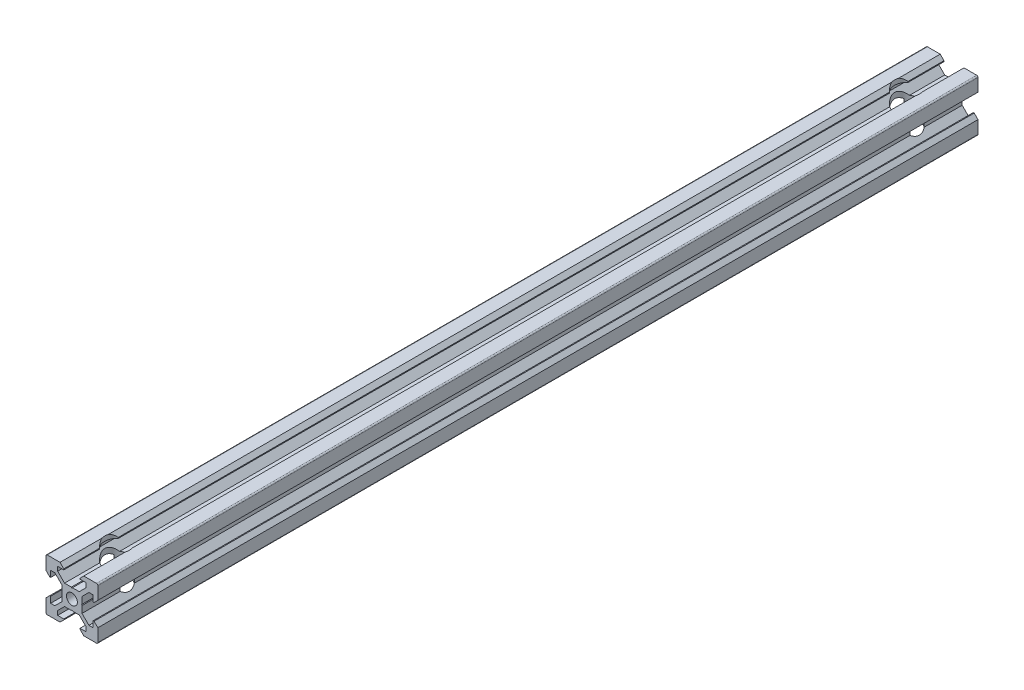
SolidWorks part; units mm, degrees
material "6063-O, Extruded Rod (SS)"
ref_plane "Front Plane" through (0, 0, 0) normal (0, 0, 1) x (1, 0, 0)
ref_plane "Top Plane" through (0, 0, 0) normal (0, 1, 0) x (1, 0, 0)
ref_plane "Right Plane" through (0, 0, 0) normal (1, 0, 0) x (0, 0, -1)
ref_plane "Plane1" through (0, 0, 0) normal (0, 0, -1) x (-1, 0, 0)
sketch "Sketch1" plane through (0, 0, 0) normal (0, 0, -1) x (-1, 0, 0)
  line L0 (-3.9, -0.21) -> (-3.9, -2.8393)
  line L1 (-3.9, -2.8393) -> (-6.5607, -5.5)
  line L2 (-6.5607, -5.5) -> (-8.2, -5.5)
  line L3 (-8.2, -5.5) -> (-8.2, -3.125)
  line L4 (-8.2, -3.125) -> (-8.545, -3.125)
  line L5 (-8.545, -3.125) -> (-10, -4.58)
  line L6 (-10, -4.58) -> (-10, -9.5)
  line L7 (-9.5, -10) -> (-4.58, -10)
  line L8 (-4.58, -10) -> (-3.125, -8.545)
  line L9 (-3.125, -8.545) -> (-3.125, -8.2)
  line L10 (-3.125, -8.2) -> (-5.5, -8.2)
  line L11 (-5.5, -8.2) -> (-5.5, -6.5607)
  line L12 (-5.5, -6.5607) -> (-2.8393, -3.9)
  line L13 (-2.8393, -3.9) -> (-0.21, -3.9)
  line L14 (-0.21, -3.9) -> (0, -3.69)
  line L15 (0, -3.69) -> (0.21, -3.9)
  line L16 (0.21, -3.9) -> (2.8393, -3.9)
  line L17 (2.8393, -3.9) -> (5.5, -6.5607)
  line L18 (5.5, -6.5607) -> (5.5, -8.2)
  line L19 (5.5, -8.2) -> (3.125, -8.2)
  line L20 (3.125, -8.2) -> (3.125, -8.545)
  line L21 (3.125, -8.545) -> (4.58, -10)
  line L22 (4.58, -10) -> (9.5, -10)
  line L23 (10, -9.5) -> (10, -4.58)
  line L24 (10, -4.58) -> (8.545, -3.125)
  line L25 (8.545, -3.125) -> (8.2, -3.125)
  line L26 (8.2, -3.125) -> (8.2, -5.5)
  line L27 (8.2, -5.5) -> (6.5607, -5.5)
  line L28 (6.5607, -5.5) -> (3.9, -2.8393)
  line L29 (3.9, -2.8393) -> (3.9, -0.21)
  line L30 (3.9, -0.21) -> (3.69, 0)
  line L31 (3.69, 0) -> (3.9, 0.21)
  line L32 (3.9, 0.21) -> (3.9, 2.8393)
  line L33 (3.9, 2.8393) -> (6.5607, 5.5)
  line L34 (6.5607, 5.5) -> (8.2, 5.5)
  line L35 (8.2, 5.5) -> (8.2, 3.125)
  line L36 (8.2, 3.125) -> (8.545, 3.125)
  line L37 (8.545, 3.125) -> (10, 4.58)
  line L38 (10, 4.58) -> (10, 9.5)
  line L39 (9.5, 10) -> (4.58, 10)
  line L40 (4.58, 10) -> (3.125, 8.545)
  line L41 (3.125, 8.545) -> (3.125, 8.2)
  line L42 (3.125, 8.2) -> (5.5, 8.2)
  line L43 (5.5, 8.2) -> (5.5, 6.5607)
  line L44 (5.5, 6.5607) -> (2.8393, 3.9)
  line L45 (2.8393, 3.9) -> (0.21, 3.9)
  line L46 (0.21, 3.9) -> (0, 3.69)
  line L47 (0, 3.69) -> (-0.21, 3.9)
  line L48 (-0.21, 3.9) -> (-2.8393, 3.9)
  line L49 (-2.8393, 3.9) -> (-5.5, 6.5607)
  line L50 (-5.5, 6.5607) -> (-5.5, 8.2)
  line L51 (-5.5, 8.2) -> (-3.125, 8.2)
  line L52 (-3.125, 8.2) -> (-3.125, 8.545)
  line L53 (-3.125, 8.545) -> (-4.58, 10)
  line L54 (-4.58, 10) -> (-9.5, 10)
  line L55 (-10, 9.5) -> (-10, 4.58)
  line L56 (-10, 4.58) -> (-8.545, 3.125)
  line L57 (-8.545, 3.125) -> (-8.2, 3.125)
  line L58 (-8.2, 3.125) -> (-8.2, 5.5)
  line L59 (-8.2, 5.5) -> (-6.5607, 5.5)
  line L60 (-6.5607, 5.5) -> (-3.9, 2.8393)
  line L61 (-3.9, 2.8393) -> (-3.9, 0.21)
  line L62 (-3.9, 0.21) -> (-3.69, 0)
  line L63 (-3.69, 0) -> (-3.9, -0.21)
  circle A0 centre (0, 0) radius 2.1
  arc A1 (-10, -9.5) -> (-9.5, -10) centre (-9.5, -9.5) ccw
  arc A2 (9.5, -10) -> (10, -9.5) centre (9.5, -9.5) ccw
  arc A3 (10, 9.5) -> (9.5, 10) centre (9.5, 9.5) ccw
  arc A4 (-9.5, 10) -> (-10, 9.5) centre (-9.5, 9.5) ccw
extrude "Boss-Extrude1" add sketch "Sketch1" against normal blind 500
ref_plane "cut plane" through (0, 0, 160.35) normal (0, 0, 1) x (1, 0, 0)
split "Split1" trim tools "cut plane" bodies to split 103 resulting bodies 105
sketch "Sketch2" plane through (0, 10, 0) normal (0, 1, 0) x (1, 0, 0)
  line L0 (0, -500) -> (0, -160.35) construction
  line L1 (0, -500) -> (0, -160.35) construction
  line L2 (0, -330.175) -> (-38.7772, -330.175) construction
  circle A0 centre (0, -177.775) radius 4.7625
  circle A1 centre (0, -482.575) radius 4.7625
  dimension "D1" = 9.525
  dimension "D2" = 304.8
  dimension "D3" = 152.4
extrude "Cut-Extrude1" cut sketch "Sketch2" against normal up to surface (20 mm away) up to face at (7.04, -10, 330.175)
hole_wizard "M5x0.8 Tapped Hole1" positions "Sketch4" profile "Sketch5" tap size "M5x0.8" standard "ANSI Metric"
sketch "Sketch4" plane through (0, 0, 500) normal (0, 0, 1) x (1, 0, 0)
  point P0 (0, 0)
sketch "Sketch5" plane through (0, 0, 500) normal (1, 0, 0) x (0, -1, 0)
  line L0 (0, 0) -> (0, 15.2318)
  line L1 (0, 15.2318) -> (2.1, 13.97)
  line L2 (2.1, 13.97) -> (2.1, 0)
  line L5 (2.1, 0) -> (0, 0)
  line L10 (0, 15.2318) -> (-2.1, 13.97) construction
  line L11 (0, -6.35) -> (0, 107.95) construction
  dimension "Tap Drill Dia." = 4.2
  dimension "Tap Drill Depth" = 13.97
  dimension "Drill Angle" = 118
hole_wizard "M5x0.8 Tapped Hole2" positions "Sketch7" profile "Sketch6" tap size "M5x0.8" standard "ANSI Metric"
sketch "Sketch7" plane through (0, 0, 160.35) normal (0, 0, -1) x (-1, 0, 0)
  point P0 (0, 0)
sketch "Sketch6" plane through (0, 0, 160.35) normal (1, 0, 0) x (0, 1, 0)
  line L0 (0, 0) -> (0, 15.2318)
  line L1 (0, 15.2318) -> (2.1, 13.97)
  line L2 (2.1, 13.97) -> (2.1, 0)
  line L5 (2.1, 0) -> (0, 0)
  line L10 (0, 15.2318) -> (-2.1, 13.97) construction
  line L11 (0, -6.35) -> (0, 107.95) construction
  dimension "Tap Drill Dia." = 4.2
  dimension "Tap Drill Depth" = 13.97
  dimension "Drill Angle" = 118
